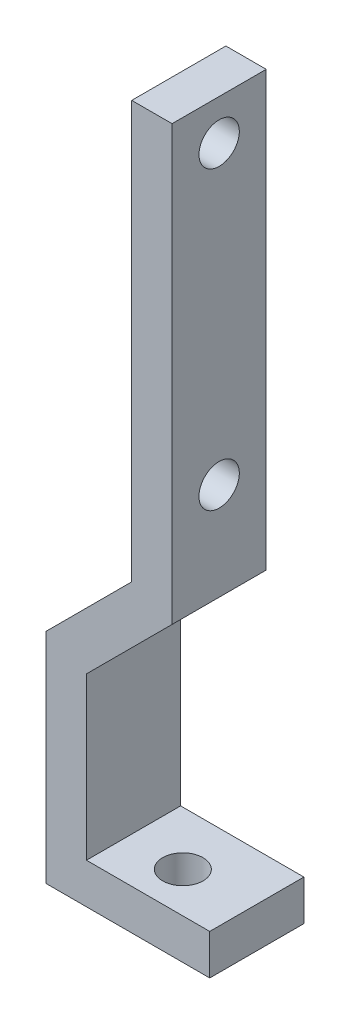
SolidWorks part; units mm, degrees
ref_plane "前视基准面" through (0, 0, 0) normal (0, 0, 1) x (1, 0, 0)
ref_plane "上视基准面" through (0, 0, 0) normal (0, 1, 0) x (1, 0, 0)
ref_plane "右视基准面" through (0, 0, 0) normal (1, 0, 0) x (0, 0, -1)
sketch "草图1" plane through (0, 0, 0) normal (0, 0, 1) x (1, 0, 0)
  line L0 (-3.6411, 21.9867) -> (-3.6411, -9.0133)
  line L1 (-3.6411, -9.0133) -> (-10.005, -15.3772)
  line L2 (-10.005, -15.3772) -> (-10.005, -31.6199)
  line L3 (-10.005, -31.6199) -> (2.1589, -31.6199)
  line L4 (2.1589, -31.6199) -> (2.1589, -28.6199)
  line L5 (2.1589, -28.6199) -> (-7.005, -28.6199)
  line L6 (-7.005, -28.6199) -> (-7.005, -16.6199)
  line L7 (-7.005, -16.6199) -> (-0.6411, -10.2559)
  line L8 (-0.6411, -10.2559) -> (-0.6411, 21.9867)
  line L9 (-0.6411, 21.9867) -> (-3.6411, 21.9867)
  line L10 (-2.8411, -28.6199) -> (-2.8411, -31.6199)
  line L11 (-4.3411, -28.6199) -> (-4.3411, -31.6199)
  line L12 (-1.3411, -28.6199) -> (-1.3411, -31.6199)
  dimension "D1" = 3
  dimension "D2" = 3
  dimension "D3" = 3
  dimension "D4" = 3
  dimension "D5" = 31
  dimension "D6" = 12
  dimension "D7" = 9
  dimension "D8" = 1.5
  dimension "D9" = 1.5
  dimension "D10" = 0.8
  dimension "D11" = 5
extrude "凸台-拉伸1" add sketch "草图1" along normal blind 7 contours L11 L5 L6 L7 L8 L9 L0 L1 L2 L3 | L12 L5 L10 L3 | L5 L11 L3 L10 | L5 L12 L3 L4 region at (-2.1411, 21.4425, 0) region at (-3.5911, -30.1199, 0) region at (-2.0911, -30.1199, 0) region at (0.4089, -30.1199, 0)
sketch "草图2" plane through (-3.6411, 0, 0) normal (-1, 0, 0) x (0, 0, 1)
  line L0 (7, 21.9867) -> (0, 21.9867) construction
  line L1 (0, 21.9867) -> (0, -9.0133) construction
  circle A0 centre (3.5, 18.9867) radius 1.5
  circle A1 centre (3.5, -3.0133) radius 1.5
  dimension "D2" = 3
  dimension "D3" = 3
  dimension "D1" = 3
  dimension "D4" = 22
  dimension "D5" = 3.5
  dimension "D6" = 3.5
extrude "切除-拉伸2" cut sketch "草图2" against normal blind 7
sketch "草图4" plane through (0, -28.6199, 0) normal (0, 1, 0) x (1, 0, 0)
  line L0 (2.1589, 0) -> (-7.005, 0) construction
  line L1 (2.1589, -7) -> (2.1589, 0) construction
  circle A0 centre (-2.8411, -4) radius 1.5
  dimension "D2" = 3
  dimension "D1" = 4
  dimension "D3" = 5
extrude "切除-拉伸3" cut sketch "草图4" against normal blind 7
